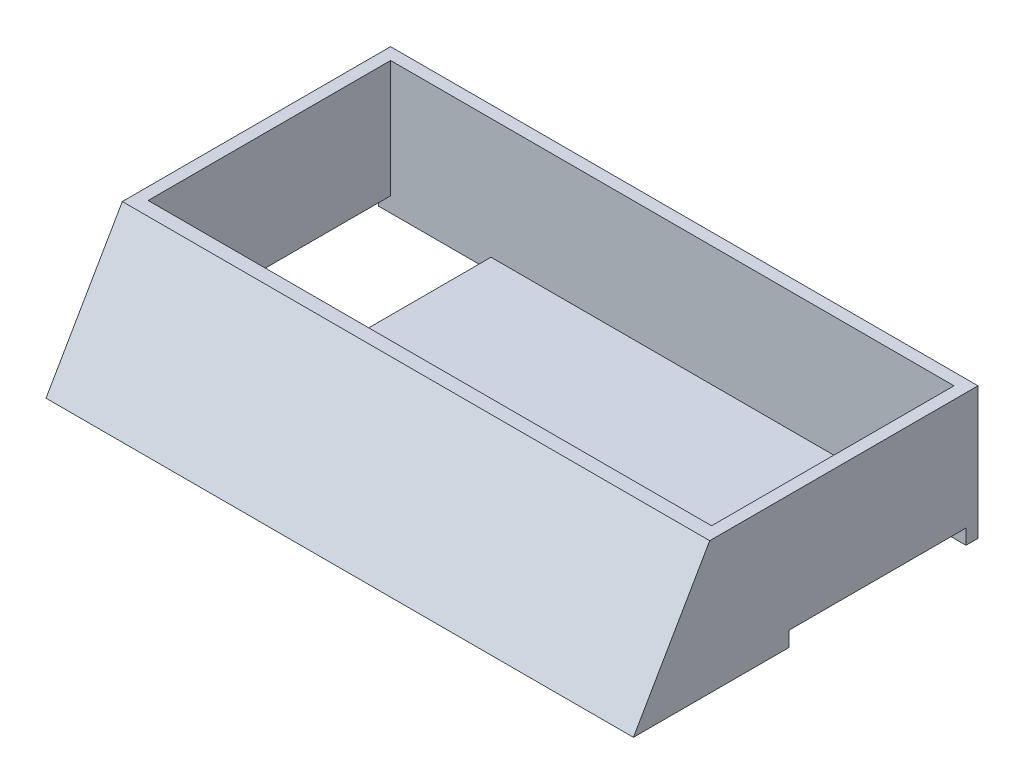
SolidWorks part; units mm, degrees
ref_plane "Alzado" through (0, 0, 0) normal (0, 0, 1) x (1, 0, 0)
ref_plane "Planta" through (0, 0, 0) normal (0, 1, 0) x (1, 0, 0)
ref_plane "Vista lateral" through (0, 0, 0) normal (1, 0, 0) x (0, 0, -1)
sketch "Croquis1" plane through (0, 0, 0) normal (1, 0, 0) x (0, 0, -1)
  line L0 (0, 0) -> (114.98, 0)
  line L1 (114.98, 0) -> (114.98, 44.1)
  line L2 (114.98, 44.1) -> (25.4611, 44.1)
  line L3 (0, 0) -> (25.4611, 44.1)
  line L4 (114.9845, -5.19) -> (114.9845, 15.0485) construction
  dimension "D1" = 114.98
  dimension "D2" = 44.1
  dimension "D3" = 120
extrude "Saliente-Extruir1" add sketch "Croquis1" along normal blind 196
shell "Vaciado1" thickness 4 removed face at (98, 44.1, -70.2206)
sketch "Croquis2" plane through (0, 0, 0) normal (0, -1, 0) x (-1, 0, 0)
  line L0 (-196, 114.98) -> (0, 114.98) construction
  line L1 (-37.5, 51.9947) -> (0, 51.9947)
  line L2 (-37.5, 51.9947) -> (-37.5, 110.98)
  line L3 (-37.5, 110.98) -> (0, 110.98)
  line L4 (0, 51.9947) -> (0, 110.98)
  line L5 (-37.5, 51.9947) -> (0, 110.98) construction
  line L6 (-37.5, 110.98) -> (0, 51.9947) construction
  line L7 (-196, 110.98) -> (-158.5, 110.98)
  line L8 (-196, 110.98) -> (-196, 51.9947)
  line L9 (-196, 51.9947) -> (-158.5, 51.9947)
  line L10 (-158.5, 110.98) -> (-158.5, 51.9947)
  line L11 (-196, 110.98) -> (-158.5, 51.9947) construction
  line L12 (-196, 51.9947) -> (-158.5, 110.98) construction
  point P4 (-18.75, 81.4873)
  point P11 (-177.25, 81.4873)
  point P12 (-196, 114.98)
  dimension "D1" = 4
  dimension "D2" = 4
extrude "Cortar-Extruir1" cut sketch "Croquis2" against normal blind 5
